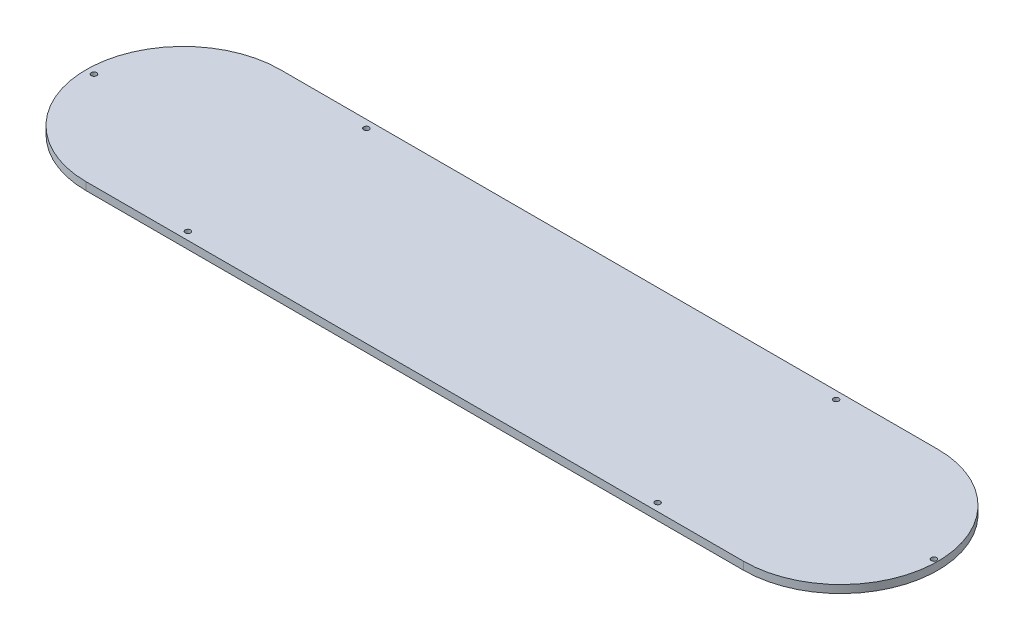
SolidWorks part; units mm, degrees
ref_plane "Front Plane" through (0, 0, 0) normal (0, 0, 1) x (1, 0, 0)
ref_plane "Top Plane" through (0, 0, 0) normal (0, 1, 0) x (1, 0, 0)
ref_plane "Right Plane" through (0, 0, 0) normal (1, 0, 0) x (0, 0, -1)
sketch "Sketch1" plane through (0, 0, 0) normal (0, 1, 0) x (1, 0, 0)
  line L0 (0, 39.37) -> (266.7, 39.37)
  line L1 (0, -39.37) -> (266.7, -39.37)
  line L2 (0, 0) -> (266.7, 0) construction
  arc A0 (0, 39.37) -> (0, -39.37) centre (0, 0) ccw
  arc A1 (266.7, -39.37) -> (266.7, 39.37) centre (266.7, 0) ccw
  circle A2 centre (38.1, 36.195) radius 1.0922
  circle A3 centre (228.6, 36.195) radius 1.0922
  circle A4 centre (38.1, -36.195) radius 1.0922
  circle A5 centre (228.6, -36.195) radius 1.0922
  circle A6 centre (-36.195, 0) radius 1.0922
  circle A7 centre (304.4825, 0) radius 1.0922
  dimension "D1" = 78.74
  dimension "D7" = 2.1844
  dimension "D8" = 2.1844
  dimension "D9" = 2.1844
  dimension "D10" = 2.1844
  dimension "D2" = 266.7
  dimension "D4" = 38.1
  dimension "D5" = 38.1
  dimension "D6" = 3.175
  dimension "D11" = 3.175
  dimension "D12" = 1.5875
extrude "Boss-Extrude1" add sketch "Sketch1" along normal blind 3.175
